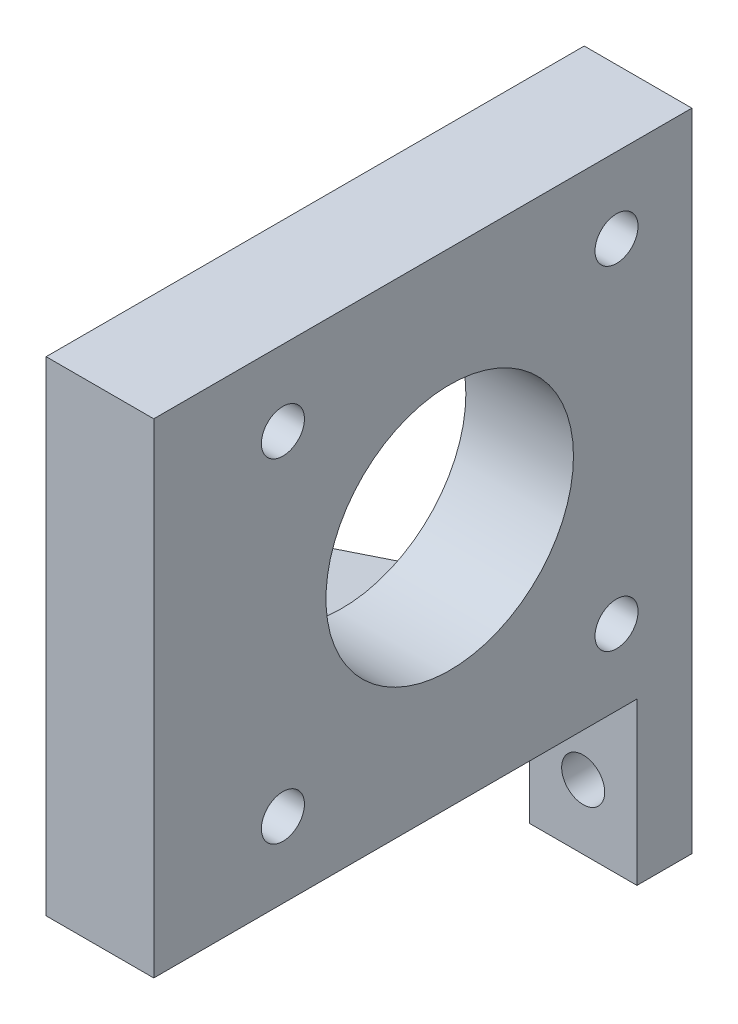
SolidWorks part; units mm, degrees
ref_plane "Front Plane" through (0, 0, 0) normal (0, 0, 1) x (1, 0, 0)
ref_plane "Top Plane" through (0, 0, 0) normal (0, 1, 0) x (1, 0, 0)
ref_plane "Right Plane" through (0, 0, 0) normal (1, 0, 0) x (0, 0, -1)
sketch "Sketch1" plane through (0, 0, 0) normal (0, 1, 0) x (1, 0, 0)
  line L1 (0, 0) -> (-10, 0)
  line L2 (0, 0) -> (0, -50)
  line L3 (0, -50) -> (-10, -50)
  line L4 (-10, 0) -> (-10, -50)
  dimension "D1" = 10
  dimension "D2" = 50
extrude "Boss-Extrude1" add sketch "Sketch1" along normal blind 60
sketch "Sketch2" plane through (0, 0, 0) normal (1, 0, 0) x (0, 0, -1)
  line L0 (-50, 60) -> (0, 60) construction
  line L1 (0, 60) -> (0, 0) construction
  line L2 (0, 37.5) -> (-50, 37.5) construction
  line L3 (-50, 60) -> (-50, 0) construction
  line L4 (-22.5, 60) -> (-22.5, 0) construction
  line L5 (-50, 0) -> (0, 0) construction
  circle A0 centre (-7, 53) radius 2
  circle A1 centre (-7, 22) radius 2
  circle A2 centre (-38, 53) radius 2
  circle A3 centre (-38, 22) radius 2
  circle A4 centre (-22.5, 37.5) radius 11.5
  dimension "D1" = 4
  dimension "D2" = 7
  dimension "D3" = 7
  dimension "D6" = 23
  dimension "D7" = 0
  dimension "D8" = 0
  dimension "D4" = 15.5
  dimension "D5" = 15.5
extrude "Cut-Extrude2" cut sketch "Sketch2" against normal blind 60
sketch "Sketch4" plane through (0, 0, 0) normal (1, 0, 0) x (0, 0, -1)
  line L1 (-50, 0) -> (-5.1, 0)
  line L2 (-50, 0) -> (-50, 15)
  line L3 (-50, 15) -> (-5.1, 15)
  line L4 (-5.1, 0) -> (-5.1, 15)
  circle A0 centre (-22.5, 37.5) radius 11.5 construction
  dimension "D1" = 15
  dimension "D2" = 17.4
extrude "Cut-Extrude3" cut sketch "Sketch4" against normal blind 60
sketch "Sketch5" plane through (-10, 0, 0) normal (-1, 0, 0) x (0, 0, 1)
  line L0 (5.1, 15) -> (50, 15) construction
  line L1 (14, 15) -> (31, 15)
  line L2 (14, 15) -> (14, 20)
  line L3 (14, 20) -> (31, 20)
  line L4 (31, 15) -> (31, 20)
  circle A0 centre (7, 22) radius 2 construction
  circle A1 centre (38, 22) radius 2 construction
  dimension "D2" = 7
  dimension "D1" = 7
  dimension "D3" = 5
extrude "Boss-Extrude3" add sketch "Sketch5" along normal blind 15
sketch "Sketch6" plane through (0, 0, 31) normal (0, 0, 1) x (1, 0, 0)
  line L0 (-10, 20) -> (-10, 25)
  line L1 (-10, 25) -> (-25, 20)
  line L2 (-25, 20) -> (-10, 20)
  dimension "D1" = 5
extrude "Boss-Extrude4" add sketch "Sketch6" against normal up to vertex (17 mm away) up to point (-25, 20, 14)
sketch "Sketch7" plane through (0, 15, 0) normal (0, -1, 0) x (1, 0, 0)
  line L0 (-25, 14) -> (-10, 14) construction
  line L1 (-25, 14) -> (-25, 31) construction
  circle A0 centre (-17.5, 22.5) radius 2
  dimension "D1" = 8.5
  dimension "D2" = 7.5
  dimension "D3" = 4
extrude "Cut-Extrude4" cut sketch "Sketch7" against normal blind 15
sketch "Sketch8" plane through (0, 0, 0) normal (0, 0, -1) x (-1, 0, 0)
  line L0 (0, 0) -> (10, 0) construction
  line L1 (10, 60) -> (10, 0) construction
  circle A0 centre (5, 6) radius 2
  dimension "D1" = 4
  dimension "D2" = 6
  dimension "D3" = 5
extrude "Cut-Extrude5" cut sketch "Sketch8" against normal blind 15
